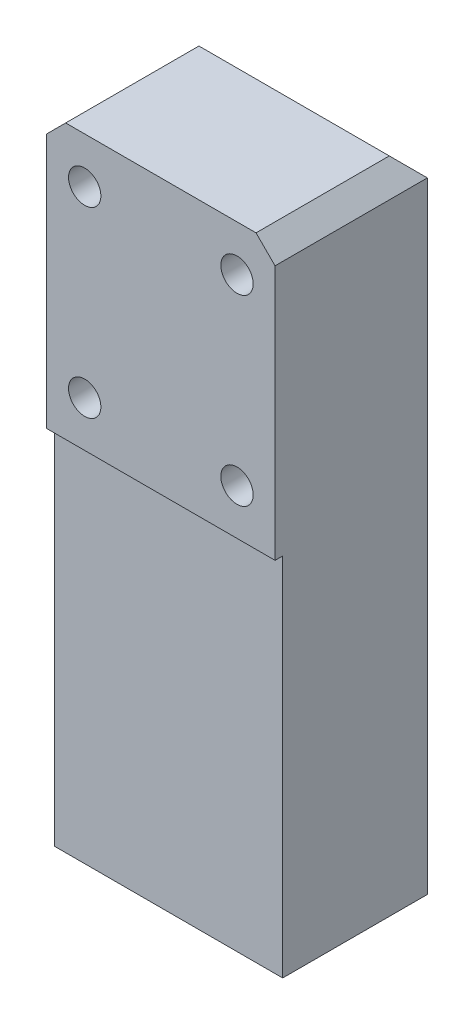
SolidWorks part; units mm, degrees
ref_plane "Alzado" through (0, 0, 0) normal (0, 0, 1) x (1, 0, 0)
ref_plane "Planta" through (0, 0, 0) normal (0, 1, 0) x (1, 0, 0)
ref_plane "Vista lateral" through (0, 0, 0) normal (1, 0, 0) x (0, 0, -1)
sketch "Croquis1" plane through (0, 0, 0) normal (1, 0, 0) x (0, 0, -1)
  line L0 (0, 0) -> (-40, 0)
  line L1 (-40, 0) -> (-40, -72)
  line L2 (-40, -72) -> (-38, -72)
  line L3 (-38, -72) -> (-38, -168)
  line L4 (-38, -168) -> (0, -168)
  line L5 (0, -168) -> (0, 0)
  dimension "D1" = 168
  dimension "D2" = 72
  dimension "D3" = 40
  dimension "D4" = 38
extrude "Saliente-Extruir1" add sketch "Croquis1" along normal blind 30 and the other way blind 30
chamfer "Chaflán1" distance 5 angle 45 1 edges at (0, 0, 0)
chamfer "Chaflán2" distance 5 angle 45 2 edges at (30, 0, 22.5) (-30, 0, 22.5)
sketch "Croquis2" plane through (0, 0, 0) normal (0, 0, -1) x (-1, 0, 0)
  line L0 (-30, -168) -> (-30, -5) construction
  line L1 (30, -168) -> (30, -5) construction
  line L3 (-25, 0) -> (25, 0) construction
  circle A0 centre (-20, -12) radius 6.5
  circle A1 centre (20, -12) radius 6.5
  circle A2 centre (-20, -60) radius 6.5
  circle A3 centre (20, -60) radius 6.5
  dimension "D1" = 13
  dimension "D2" = 13
  dimension "D3" = 13
  dimension "D4" = 13
  dimension "D5" = 10
  dimension "D6" = 10
  dimension "D7" = 10
  dimension "D8" = 10
  dimension "D9" = 12
  dimension "D10" = 48
  dimension "D11" = 12
  dimension "D12" = 48
extrude "Cortar-Extruir1" cut sketch "Croquis2" against normal blind 9
sketch "Croquis3" plane through (0, 0, 9) normal (0, 0, -1) x (-1, 0, 0)
  circle A0 centre (-20, -12) radius 4.25
  circle A1 centre (20, -12) radius 4.25
  circle A2 centre (20, -60) radius 4.25
  circle A3 centre (-20, -60) radius 4.25
  dimension "D1" = 8.5
  dimension "D2" = 8.5
  dimension "D3" = 8.5
  dimension "D4" = 8.5
extrude "Cortar-Extruir2" cut sketch "Croquis3" against normal up to next
sketch "Croquis4" plane through (0, -168, 0) normal (0, -1, 0) x (1, 0, 0)
  line L0 (-30, 0) -> (30, 0) construction
  circle A0 centre (-22, 30) radius 4
  circle A1 centre (-22, 8) radius 4
  circle A2 centre (22, 30) radius 4
  circle A3 centre (22, 8) radius 4
  dimension "D1" = 8
  dimension "D2" = 8
  dimension "D3" = 8
  dimension "D4" = 8
  dimension "D5" = 22
  dimension "D6" = 22
  dimension "D7" = 22
  dimension "D8" = 22
  dimension "D9" = 8
  dimension "D10" = 8
  dimension "D11" = 22
  dimension "D12" = 22
extrude "Cortar-Extruir3" cut sketch "Croquis4" against normal blind 30
